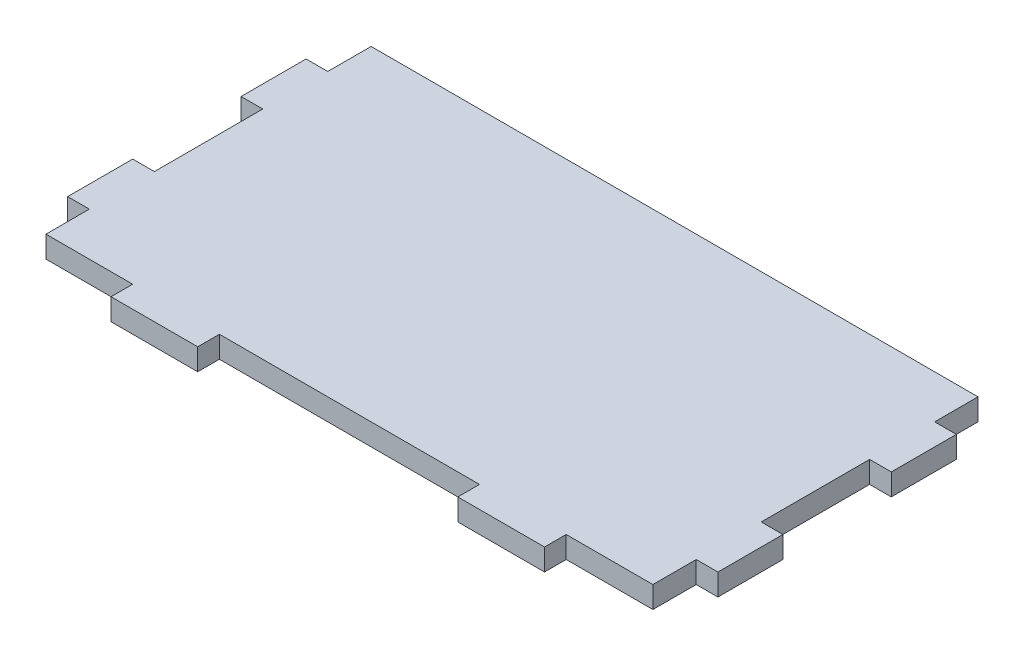
SolidWorks part; units mm, degrees
ref_plane "Front Plane" through (0, 0, 0) normal (0, 0, 1) x (1, 0, 0)
ref_plane "Top Plane" through (0, 0, 0) normal (0, 1, 0) x (1, 0, 0)
ref_plane "Right Plane" through (0, 0, 0) normal (1, 0, 0) x (0, 0, -1)
sketch "Sketch1" plane through (0, 0, 0) normal (0, 1, 0) x (1, 0, 0)
  line L0 (0, 37.5) -> (0, -37.5) construction
  line L1 (-70, 37.5) -> (-50, 37.5)
  line L2 (-70, 37.5) -> (-70, 27.5)
  line L3 (-70, -37.5) -> (-50, -37.5)
  line L4 (70, 37.5) -> (70, 27.5)
  line L5 (-70, 37.5) -> (70, -37.5) construction
  line L6 (-70, -37.5) -> (70, 37.5) construction
  line L7 (-50, 37.5) -> (-30, 37.5)
  line L13 (50, 37.5) -> (30, 37.5)
  line L15 (-50, 37.5) -> (-30, 37.5) construction
  line L16 (-30, 37.5) -> (30, 37.5)
  line L17 (30, 37.5) -> (50, 37.5) construction
  line L18 (50, 37.5) -> (70, 37.5)
  line L23 (-70, 12.5) -> (-70, -12.5)
  line L24 (-70, 0) -> (70, 0) construction
  line L25 (70, -12.5) -> (75, -12.5)
  line L26 (70, 12.5) -> (70, -12.5)
  line L29 (-70, 12.5) -> (-70, -12.5) construction
  line L30 (-70, -27.5) -> (-70, -37.5)
  line L31 (70, 12.5) -> (70, -12.5) construction
  line L32 (70, -27.5) -> (70, -37.5)
  line L33 (75, -27.5) -> (75, -12.5)
  line L37 (-30, -37.5) -> (-30, -42.5)
  line L38 (-50, -42.5) -> (-30, -42.5)
  line L39 (-50, -37.5) -> (-50, -42.5)
  line L40 (-50, -37.5) -> (-30, -37.5) construction
  line L41 (-30, -37.5) -> (30, -37.5)
  line L42 (30, -37.5) -> (50, -37.5) construction
  line L43 (50, -37.5) -> (70, -37.5)
  line L44 (30, -37.5) -> (30, -42.5)
  line L45 (50, -42.5) -> (30, -42.5)
  line L46 (50, -37.5) -> (50, -42.5)
  line L47 (70, 27.5) -> (75, 27.5)
  line L48 (70, 27.5) -> (70, 12.5) construction
  line L49 (70, 12.5) -> (75, 12.5)
  line L50 (75, 27.5) -> (75, 12.5)
  line L51 (70, -27.5) -> (75, -27.5)
  line L52 (70, -27.5) -> (70, -12.5) construction
  line L53 (-70, -27.5) -> (-70, -12.5) construction
  line L54 (-70, -27.5) -> (-75, -27.5)
  line L55 (-75, -27.5) -> (-75, -12.5)
  line L56 (-70, -12.5) -> (-75, -12.5)
  line L57 (-70, 12.5) -> (-75, 12.5)
  line L58 (-75, 27.5) -> (-75, 12.5)
  line L59 (-70, 27.5) -> (-75, 27.5)
  line L60 (-70, 27.5) -> (-70, 12.5) construction
  line L61 (-70, 27.5) -> (-70, 12.5) construction
  line L62 (-70, -12.5) -> (-70, -27.5) construction
  line L63 (70, -12.5) -> (70, -27.5) construction
  line L64 (70, 27.5) -> (70, 12.5) construction
  point P0 (0, 0)
  point P7 (-70, -0.0366)
  point P8 (0, 0)
  point P19 (70, 9.0509)
  dimension "D1" = 140
  dimension "D2" = 75
  dimension "D3" = 20
  dimension "D4" = 5
  dimension "D5" = 20
  dimension "D6" = 5
  dimension "D7" = 10
  dimension "D8" = 15
extrude "Boss-Extrude1" add sketch "Sketch1" along normal blind 5
